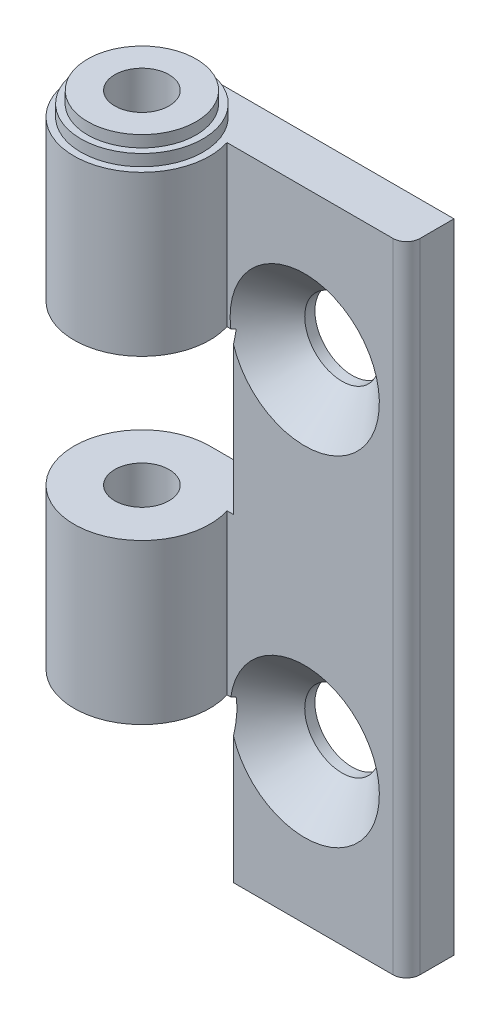
SolidWorks part; units mm, degrees
material "6063-T5"
ref_plane "Front Plane" through (0, 0, 0) normal (0, 0, 1) x (1, 0, 0)
ref_plane "Top Plane" through (0, 0, 0) normal (0, 1, 0) x (1, 0, 0)
ref_plane "Right Plane" through (0, 0, 0) normal (1, 0, 0) x (0, 0, -1)
ref_plane "Plane1" through (0, 0, 0) normal (0, 0, 1) x (1, 0, 0)
sketch "Sketch1" plane through (0, 0, 0) normal (0, 0, 1) x (1, 0, 0)
  line L0 (0, 23.5) -> (5, 23.5)
  line L1 (5, 23.5) -> (5, -23.5)
  line L2 (5, -23.5) -> (0, -23.5)
  line L3 (0, -23.5) -> (0, 23.5)
  line L4 (0, -23.5) -> (0, 23.5) construction
revolve "Revolve1" add sketch "Sketch1" angle 360 about L4 reverse direction yes
ref_plane "Plane2" through (0, 0, -5) normal (0, 0, 1) x (1, 0, 0)
sketch "Sketch2" plane through (0, 0, -5) normal (0, 0, 1) x (1, 0, 0)
  line L0 (0, 23.5) -> (0, -23.5)
  line L1 (0, -23.5) -> (18, -23.5)
  line L2 (18, -23.5) -> (18, 23.5)
  line L3 (18, 23.5) -> (0, 23.5)
extrude "Boss-Extrude1" add sketch "Sketch2" along normal blind 3.5
ref_plane "Plane3" through (0, 0, 0) normal (0, 0, 1) x (1, 0, 0)
sketch "Sketch3" plane through (0, 0, 0) normal (0, 0, 1) x (1, 0, 0)
  line L0 (-47, 47) -> (-47, -47)
  line L1 (-47, -47) -> (47, -47)
  line L2 (47, -47) -> (47, 47)
  line L3 (47, 47) -> (-47, 47)
  line L4 (-5, 23.5) -> (-5, 11.75)
  line L5 (-5, 11.75) -> (5.25, 11.75)
  line L6 (5.25, 11.75) -> (5.25, 0)
  line L7 (5.25, 0) -> (-5, 0)
  line L8 (-5, 0) -> (-5, -11.75)
  line L9 (-5, -11.75) -> (5.25, -11.75)
  line L10 (5.25, -11.75) -> (5.25, -23.5)
  line L11 (5.25, -23.5) -> (18, -23.5)
  line L12 (18, -23.5) -> (18, 23.5)
  line L13 (18, 23.5) -> (-5, 23.5)
extrude "Cut-Extrude1" cut sketch "Sketch3" against normal blind 47 and the other way blind 47
ref_plane "Plane4" through (0, 0, 0) normal (0, 0, 1) x (1, 0, 0)
sketch "Sketch4" plane through (0, 0, 0) normal (0, 0, 1) x (1, 0, 0)
  line L0 (0, 25.2) -> (4, 25.2)
  line L1 (4, 25.2) -> (4, 24.35)
  line L2 (4, 24.35) -> (4.5, 24.35)
  line L3 (4.5, 24.35) -> (4.5, 23.5)
  line L4 (4.5, 23.5) -> (0, 23.5)
  line L5 (0, 23.5) -> (0, 25.2)
  line L6 (0, 23.5) -> (0, 25.2) construction
revolve "Revolve2" add sketch "Sketch4" angle 360 about L6 reverse direction yes
ref_plane "Plane5" through (0, 0, 0) normal (0, 0, 1) x (1, 0, 0)
sketch "Sketch5" plane through (0, 0, 0) normal (0, 0, 1) x (1, 0, 0)
  line L0 (0, 26.7) -> (2, 26.7)
  line L1 (2, 26.7) -> (2, -26.7)
  line L2 (2, -26.7) -> (0, -26.7)
  line L3 (0, -26.7) -> (0, 26.7)
  line L4 (0, -26.7) -> (0, 26.7) construction
revolve "Cut-Revolve1" cut sketch "Sketch5" angle 360 about L4 reverse direction yes
ref_plane "Plane6" through (10.5, 0, 0) normal (1, 0, 0) x (0, 0, -1)
sketch "Sketch6" plane through (10.5, 0, 0) normal (1, 0, 0) x (0, 0, -1)
  line L0 (5, -12.5) -> (5, -15.25)
  line L1 (5, -15.25) -> (4.25, -15.25)
  line L2 (4.25, -15.25) -> (1.5, -18)
  line L3 (1.5, -18) -> (1.5, -12.5)
  line L4 (1.5, -12.5) -> (5, -12.5)
  line L5 (1.5, -12.5) -> (5, -12.5) construction
revolve "Cut-Revolve2" cut sketch "Sketch6" angle 360 about L5 reverse direction yes
ref_plane "Plane7" through (10.5, 0, 0) normal (1, 0, 0) x (0, 0, -1)
sketch "Sketch7" plane through (10.5, 0, 0) normal (1, 0, 0) x (0, 0, -1)
  line L0 (5, 12.5) -> (5, 9.75)
  line L1 (5, 9.75) -> (4.25, 9.75)
  line L2 (4.25, 9.75) -> (1.5, 7)
  line L3 (1.5, 7) -> (1.5, 12.5)
  line L4 (1.5, 12.5) -> (5, 12.5)
  line L5 (1.5, 12.5) -> (5, 12.5) construction
revolve "Cut-Revolve3" cut sketch "Sketch7" angle 360 about L5 reverse direction yes
ref_plane "Plane8" through (0, 0, 0) normal (0, 1, 0) x (1, 0, 0)
sketch "Sketch8" plane through (0, 0, 0) normal (0, 1, 0) x (1, 0, 0)
  line L0 (17, 1.5) -> (18, 1.5)
  line L1 (18, 1.5) -> (18, 2.5)
  arc A0 (18, 2.5) -> (17, 1.5) centre (17, 2.5) cw
extrude "Cut-Extrude2" cut sketch "Sketch8" against normal blind 23.5 and the other way blind 23.5
